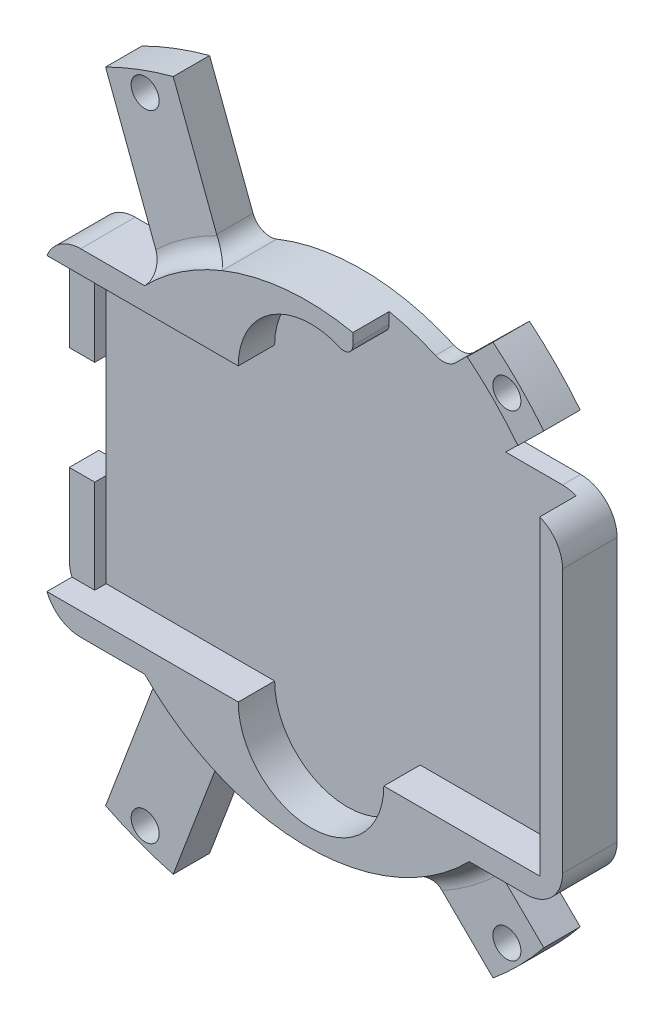
SolidWorks part; units mm, degrees
ref_plane "Front Plane" through (0, 0, 0) normal (0, 0, 1) x (1, 0, 0)
ref_plane "Top Plane" through (0, 0, 0) normal (0, 1, 0) x (1, 0, 0)
ref_plane "Right Plane" through (0, 0, 0) normal (1, 0, 0) x (0, 0, -1)
sketch "Sketch1" plane through (0, 0, 0) normal (0, 0, 1) x (1, 0, 0)
  line L1 (3.175, -2.2225) -> (68.175, -2.2225)
  line L2 (3.175, -2.2225) -> (3.175, 38.4125)
  line L3 (3.175, 38.4125) -> (68.175, 38.4125)
  line L4 (68.175, -2.2225) -> (68.175, 38.4125)
  line L5 (4.064, -5.3975) -> (66.27, -5.3975)
  line L6 (-1.016, -0.3175) -> (-1.016, 36.5075)
  line L7 (4.064, 41.5875) -> (66.27, 41.5875)
  line L8 (71.35, -0.3175) -> (71.35, 36.5075)
  line L12 (68.175, -1.905) -> (3.175, -1.905) construction
  line L13 (3.175, 38.095) -> (42.175, 38.095) construction
  line L15 (5.0041, 62.7587) -> (13.0047, 41.5875)
  line L16 (14.452, 66.3291) -> (23.8018, 41.5875)
  line L17 (6.7999, 58.0067) -> (5.0041, 62.7587) construction
  line L18 (14.452, 66.3291) -> (16.2478, 61.5771) construction
  line L19 (59.1124, 56.538) -> (43.9345, 41.5875)
  line L20 (55.4933, 52.9731) -> (59.1124, 56.538) construction
  line L21 (66.2001, 49.3426) -> (58.3271, 41.5875)
  line L22 (66.2001, 49.3426) -> (62.581, 45.7777) construction
  line L23 (5.0041, -26.5687) -> (13.0047, -5.3975)
  line L24 (5.0041, -26.5687) -> (6.7999, -21.8167) construction
  line L25 (14.452, -30.1391) -> (23.8018, -5.3975)
  line L26 (16.2478, -25.3871) -> (14.452, -30.1391) construction
  line L27 (59.1124, -20.348) -> (43.9345, -5.3975)
  line L28 (59.1124, -20.348) -> (55.4933, -16.7831) construction
  line L29 (66.2001, -13.1526) -> (58.3271, -5.3975)
  line L30 (62.581, -9.5877) -> (66.2001, -13.1526) construction
  arc A0 (4.064, -5.3975) -> (-1.016, -0.3175) centre (4.064, -0.3175) cw
  arc A1 (66.27, -5.3975) -> (71.35, -0.3175) centre (66.27, -0.3175) ccw
  arc A2 (-1.016, 36.5075) -> (4.064, 41.5875) centre (4.064, 36.5075) cw
  arc A3 (66.27, 41.5875) -> (71.35, 36.5075) centre (66.27, 36.5075) cw
  arc A4 (5.0041, 62.7587) -> (14.452, 66.3291) centre (27.281, 18.095) cw
  circle A5 centre (27.281, 18.095) radius 49.911 construction
  circle A6 centre (10.5303, 62.4211) radius 1.9558
  circle A7 centre (10.5303, 62.4211) radius 1.9558 construction
  arc A8 (59.1124, 56.538) -> (66.2001, 49.3426) centre (27.281, 18.095) cw
  circle A9 centre (61.0395, 51.3478) radius 1.9558
  circle A10 centre (61.0395, 51.3478) radius 1.9558 construction
  arc A11 (5.0041, -26.5687) -> (14.452, -30.1391) centre (27.281, 18.095) ccw
  circle A12 centre (10.5303, -26.2311) radius 1.9558
  circle A13 centre (10.5303, -26.2311) radius 1.9558 construction
  arc A14 (66.2001, -13.1526) -> (59.1124, -20.348) centre (27.281, 18.095) cw
  circle A15 centre (61.0395, -15.1578) radius 1.9558
  circle A16 centre (61.0395, -15.1578) radius 1.9558 construction
  point P25 (0, 0)
  dimension "D1" = 5.08
  dimension "D2" = 0.3175
  dimension "D3" = 0.3175
  dimension "D4" = 3.175
  dimension "D5" = 5.2305
  dimension "D6" = 3.175
  dimension "D7" = 3.175
  dimension "D8" = 4.191
extrude "Boss-Extrude1" add sketch "Sketch1" along normal blind 2.54 contours L5 L8 L7 L6 L4 L1 L2 L3 | L2 L3 L4 L1 region at (1.082, -3.2995, 0)
extrude "Boss-Extrude2" add sketch "Sketch1<4>" along normal blind 7.62 contours A3 L7 A2 L6 A0 L5 A1 L8 L4 L1 L2 L3 region at (1.082, -3.2995, 0)
sketch "Sketch1<4>" plane through (0, 0, 0) normal (0, 0, 1) x (1, 0, 0) same geometry as "Sketch1"
extrude "Boss-Extrude3" add sketch "Sketch1<6>" along normal blind 5.08 contours A4 L15 L7 L16 A6 | A8 L19 L7 L21 A9 | A14 L29 L5 L27 A15 | L23 A11 L25 L5 A12 region at (14.3496, -16.5107, 0) region at (56.0285, -11.0209, 0) region at (14.3496, 52.7007, 0) region at (56.0285, 47.2109, 0)
sketch "Sketch1<6>" plane through (0, 0, 0) normal (0, 0, 1) x (1, 0, 0) same geometry as "Sketch1"
sketch "Sketch3" plane through (0, 0, 0) normal (0, 0, 1) x (1, 0, 0)
  line L0 (35.6659, 51.1125) -> (35.6659, 41.5875) construction
  line L1 (4.064, 41.5875) -> (66.27, 41.5875) construction
  line L2 (13.0047, 41.5875) -> (58.3271, 41.5875)
  line L3 (35.6659, -14.9225) -> (35.6659, -5.3975) construction
  line L4 (4.064, -5.3975) -> (66.27, -5.3975) construction
  line L5 (13.0047, -5.3975) -> (58.3271, -5.3975)
  arc A0 (13.0047, 41.5875) -> (58.3271, 41.5875) centre (35.6659, 19.3931) cw
  arc A1 (13.0047, -5.3975) -> (58.3271, -5.3975) centre (35.6659, 16.7969) ccw
  dimension "D1" = 9.525
  dimension "D2" = 9.525
extrude "Boss-Extrude4" add sketch "Sketch3" along normal blind 7.62
fillet "Fillet2" radius 2.54 8 edges at (50.0849, 47.6458, 2.54) (54.4518, 44.9511, 5.08) (16.9807, 45.0248, 5.08) (21.4698, 47.7584, 2.54) (16.9807, -8.8348, 5.08) (21.4698, -11.5684, 2.54) (50.0849, -11.4558, 2.54) (54.4518, -8.7611, 5.08)
sketch "Sketch4" plane through (0, 0, 7.62) normal (0, 0, 1) x (1, 0, 0)
  line L0 (3.175, 38.4125) -> (68.175, 38.4125) construction
  line L1 (36.2338, 48.5725) -> (36.2338, 38.4125) construction
  line L2 (36.2338, 51.1074) -> (36.2338, 48.5725) construction
  line L3 (3.175, 18.095) -> (68.175, 18.095) construction
  line L4 (46.3938, 38.4125) -> (26.0738, 38.4125)
  line L6 (3.175, -2.2225) -> (3.175, 38.4125) construction
  line L7 (68.175, -2.2225) -> (68.175, 38.4125) construction
  line L8 (46.3938, -2.2225) -> (26.0738, -2.2225)
  arc A0 (26.0738, 38.4125) -> (46.3938, 38.4125) centre (36.2338, 38.4125) cw
  arc A1 (48.5393, 48.3827) -> (23.8386, 48.825) centre (35.6659, 19.3931) ccw construction
  arc A3 (26.0738, -2.2225) -> (46.3938, -2.2225) centre (36.2338, -2.2225) ccw
  dimension "D2" = 10.16
  dimension "D1" = 10.16
extrude "Cut-Extrude2" cut sketch "Sketch4" against normal blind 5.08
sketch "Sketch5" plane through (0, 0, 7.62) normal (0, 0, 1) x (1, 0, 0)
  line L0 (3.175, -2.2225) -> (3.175, 38.4125) construction
  line L1 (3.175, -2.2225) -> (-1.016, -2.2225)
  line L2 (3.175, -2.2225) -> (3.175, 38.4125)
  line L3 (3.175, 38.4125) -> (-1.016, 38.4125)
  line L4 (-1.016, -2.2225) -> (-1.016, 38.4125)
  line L5 (26.0738, 38.4125) -> (3.175, 38.4125) construction
  line L6 (26.0738, -2.2225) -> (3.175, -2.2225) construction
  line L8 (-1.016, -0.3175) -> (-1.016, 36.5075) construction
extrude "Cut-Extrude3" cut sketch "Sketch5" against normal blind 5.08 contours L4 L3 L2 L1
sketch "Sketch6" plane through (0, 0, 2.54) normal (0, 0, 1) x (1, 0, 0)
  line L7 (2.54, 38.4125) -> (2.54, -2.2225)
  line L8 (26.0738, 38.4125) -> (-0.6453, 38.4125) construction
  line L9 (-0.6453, -2.2225) -> (26.0738, -2.2225) construction
  line L10 (-1.016, -0.3175) -> (-1.016, 36.5075) construction
  line L14 (-0.6453, 38.4125) -> (2.54, 38.4125)
  line L15 (-1.016, 36.5075) -> (-1.016, -0.3175)
  line L16 (-1.016, 36.5075) -> (-1.016, -0.3175)
  line L17 (2.54, -2.2225) -> (-0.6453, -2.2225)
  arc A5 (-1.016, -0.3175) -> (-0.6453, -2.2225) centre (4.064, -0.3175) ccw
  arc A6 (-0.6453, 38.4125) -> (-1.016, 36.5075) centre (4.064, 36.5075) ccw
  arc A7 (-1.016, -0.3175) -> (-0.6453, -2.2225) centre (4.064, -0.3175) ccw
  arc A8 (-0.6453, 38.4125) -> (-1.016, 36.5075) centre (4.064, 36.5075) ccw
  dimension "D1" = 3.556
  dimension "D2" = 0
extrude "Boss-Extrude5" add sketch "Sketch6" along normal blind 1.5875
sketch "Sketch7" plane through (0, 0, 7.62) normal (0, 0, 1) x (1, 0, 0)
  line L0 (42.0758, 52.9731) -> (55.4933, 52.9731)
  line L1 (68.175, 38.4125) -> (42.0758, 38.4125)
  line L2 (68.175, 38.4125) -> (68.175, 45.7777)
  line L4 (42.0758, 38.4125) -> (42.0758, 52.9731)
  line L5 (66.2001, 49.3426) -> (60.1366, 43.37) construction
  line L6 (59.1124, 56.538) -> (51.9841, 49.5165) construction
  line L7 (62.581, 45.7777) -> (68.175, 45.7777)
  arc A2 (55.4933, 52.9731) -> (62.581, 45.7777) centre (27.3018, 18.1155) cw
  dimension "D3" = 5.08
  dimension "D4" = 44.831
  dimension "D1" = 4.318
  dimension "D2" = 5.08
extrude "Cut-Extrude4" cut sketch "Sketch7" against normal blind 5.08
fillet "Fillet3" radius 1.27 1 edges at (42.0758, 46.7249, 5.08)
sketch "Sketch8" plane through (0, 0, 4.1275) normal (0, 0, 1) x (1, 0, 0)
  line L0 (2.54, -2.2225) -> (2.54, 38.4125) construction
  line L1 (-1.016, 25.334) -> (2.54, 25.334)
  line L2 (-1.016, 25.334) -> (-1.016, 10.856)
  line L3 (-1.016, 10.856) -> (2.54, 10.856)
  line L4 (2.54, 25.334) -> (2.54, 10.856)
  line L5 (-1.016, 36.5075) -> (-1.016, -0.3175) construction
  point P8 (-1.016, 18.095)
  point P9 (-1.016, 18.095)
  dimension "D1" = 14.478
extrude "Cut-Extrude5" cut sketch "Sketch8" against normal up to surface (4.1275 mm away) up to face at (35.7803, 18.095, 0)
